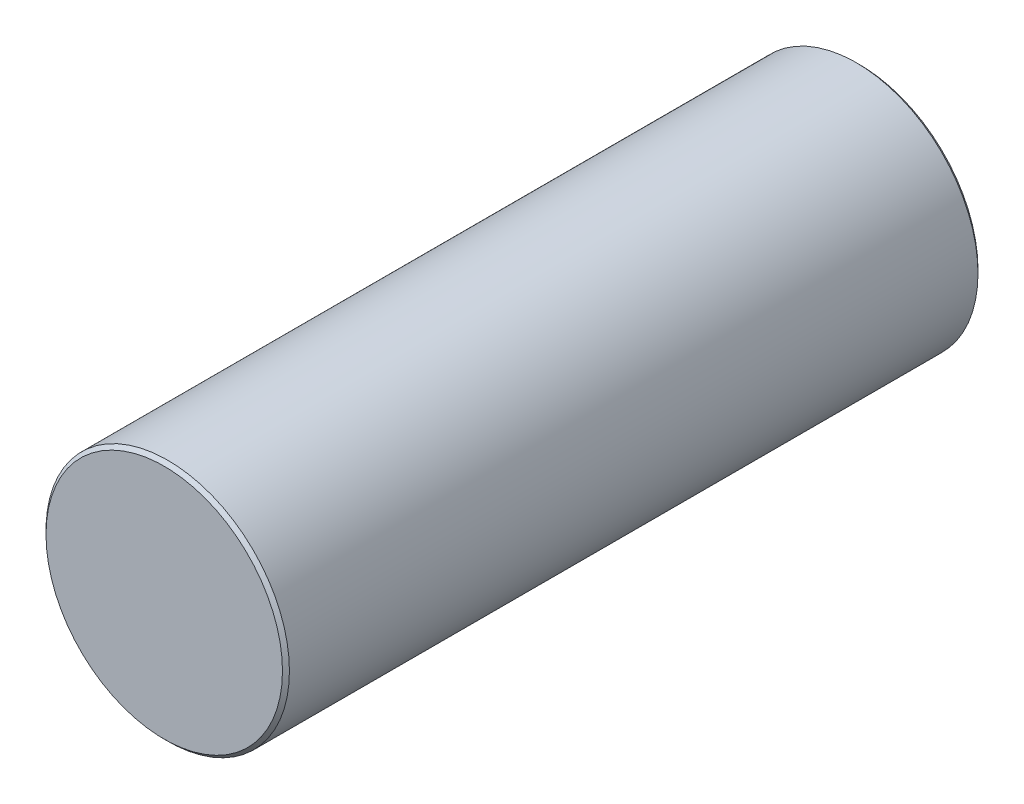
SolidWorks part; units mm, degrees
ref_plane "Front Plane" through (0, 0, 0) normal (0, 0, 1) x (1, 0, 0)
ref_plane "Top Plane" through (0, 0, 0) normal (0, 1, 0) x (1, 0, 0)
ref_plane "Right Plane" through (0, 0, 0) normal (1, 0, 0) x (0, 0, -1)
sketch "Sketch2" plane through (0, 0, 0) normal (0, 0, 1) x (1, 0, 0)
  circle A0 centre (0, 0) radius 1.75
  dimension "D1" = 3.5
extrude "Boss-Extrude1" add sketch "Sketch2" along normal blind 10
chamfer "Chamfer2" distance 0.05 angle 45 2 edges at (1.75, 0, 10) (1.75, 0, 0)
